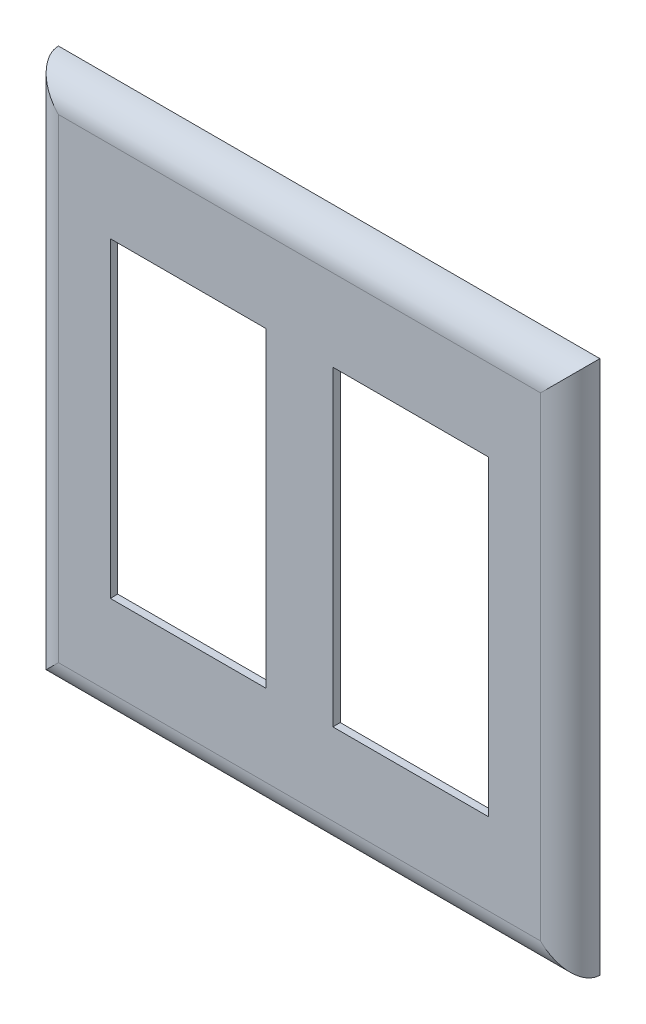
SolidWorks part; units mm, degrees
ref_plane "Front" through (0, 0, 0) normal (0, 0, 1) x (1, 0, 0)
ref_plane "Top" through (0, 0, 0) normal (0, 1, 0) x (1, 0, 0)
ref_plane "Right" through (0, 0, 0) normal (1, 0, 0) x (0, 0, -1)
sketch "Sketch1" plane through (0, 0, 0) normal (0, 0, 1) x (1, 0, 0)
  line L1 (-57.9437, 57.15) -> (57.9437, 57.15)
  line L2 (-57.9437, 57.15) -> (-57.9437, -57.15)
  line L3 (-57.9437, -57.15) -> (57.9438, -57.15)
  line L4 (57.9437, 57.15) -> (57.9438, -57.15)
  line L5 (-57.9437, 57.15) -> (57.9438, -57.15) construction
  line L6 (-57.9437, -57.15) -> (57.9437, 57.15) construction
  line L7 (-40.489, 33.3375) -> (-7.1515, 33.3375)
  line L8 (-40.489, 33.3375) -> (-40.489, -33.3375)
  line L9 (-40.489, -33.3375) -> (-7.1515, -33.3375)
  line L10 (-7.1515, 33.3375) -> (-7.1515, -33.3375)
  line L11 (7.1437, 33.3375) -> (40.4812, 33.3375)
  line L12 (7.1437, 33.3375) -> (7.1438, -33.3375)
  line L13 (7.1438, -33.3375) -> (40.4813, -33.3375)
  line L14 (40.4812, 33.3375) -> (40.4813, -33.3375)
  point P0 (0, 0)
  dimension "D1" = 115.8875
  dimension "D2" = 114.3
  dimension "D3" = 50.7923
  dimension "D4" = 50.8
  dimension "D5" = 33.3375
  dimension "D6" = 66.675
  dimension "D7" = 23.8125
  dimension "D8" = 23.8125
extrude "Boss-Extrude1" add sketch "Sketch1" along normal blind 6.35
sketch "Sketch2" plane through (0, 0, 0) normal (0, 0, -1) x (-1, 0, 0)
  line L16 (-56.3563, -55.5625) -> (56.3562, -55.5625)
  line L17 (56.3562, -55.5625) -> (56.3562, 55.5625)
  line L18 (56.3562, 55.5625) -> (-56.3562, 55.5625)
  line L19 (-56.3562, 55.5625) -> (-56.3563, -55.5625)
  line L20 (-56.3563, -55.5625) -> (56.3562, -55.5625)
  line L21 (56.3562, -55.5625) -> (56.3562, 55.5625)
  line L22 (56.3562, 55.5625) -> (-56.3562, 55.5625)
  line L23 (-56.3562, 55.5625) -> (-56.3563, -55.5625)
  dimension "D1" = 1.5875
extrude "Cut-Extrude1" cut sketch "Sketch2" against normal blind 4.7625
fillet "Fillet2" radius 6.35 8 edges at (0, 57.15, 6.35) (-57.9437, 0, 6.35) (0, -57.15, 6.35) (57.9438, 0, 6.35) (0, -55.5625, 4.7625) (-56.3562, 0, 4.7625) (0, 55.5625, 4.7625) (56.3563, 0, 4.7625)
